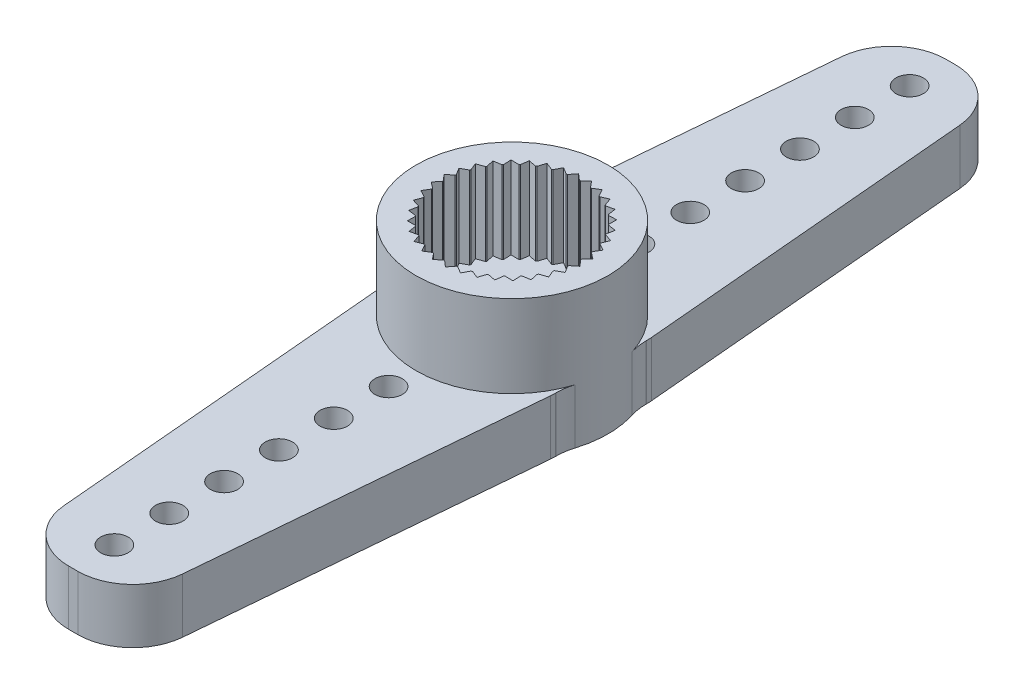
SolidWorks part; units mm, degrees
ref_plane "Front Plane" through (0, 0, 0) normal (0, 0, 1) x (1, 0, 0)
ref_plane "Top Plane" through (0, 0, 0) normal (0, 1, 0) x (1, 0, 0)
ref_plane "Right Plane" through (0, 0, 0) normal (1, 0, 0) x (0, 0, -1)
sketch "Sketch1" plane through (0, 0, 0) normal (0, 1, 0) x (1, 0, 0)
  line L0 (-21.777, 0) -> (33.3507, 0) construction
  line L1 (0, 26.1309) -> (0, -34.4991) construction
  line L2 (-17.4191, 16) -> (29.5794, 16) construction
  line L3 (-18.8664, -16) -> (33.3507, -16) construction
  line L4 (8.5, 26.926) -> (8.5, -27.618) construction
  line L5 (-8.5, 31.6087) -> (-8.5, -32.3009) construction
  line L6 (-24.067, 1.75) -> (35.98, 1.75) construction
  line L7 (-24.067, -1.75) -> (33.3507, -1.75) construction
  line L8 (-3.25, 29.5018) -> (-3.25, -36.5148) construction
  line L9 (3.25, 29.5018) -> (3.25, -33.8811) construction
  line L10 (-2, 29.5018) -> (-2, -51.2631) construction
  line L11 (2, 29.5018) -> (2, -51.2631) construction
  line L12 (-3.25, -1.75) -> (-3.25, 1.75)
  line L13 (-3.25, 1.75) -> (-2, 16)
  line L14 (-2, 16) -> (2, 16)
  line L15 (2, 16) -> (3.25, 1.75)
  line L16 (3.25, -1.75) -> (3.25, 1.75)
  line L19 (3.25, -1.75) -> (2, -16)
  line L20 (2, -16) -> (-2, -16)
  line L21 (-2, -16) -> (-3.25, -1.75)
  dimension "D1" = 16
  dimension "D2" = 16
  dimension "D3" = 8.5
  dimension "D4" = 8.5
  dimension "D5" = 1.75
  dimension "D6" = 1.75
  dimension "D7" = 3.25
  dimension "D8" = 3.25
  dimension "D9" = 2
  dimension "D10" = 2
extrude "Boss-Extrude1" add sketch "Sketch1" along normal blind 2
fillet "Fillet1" radius 2 4 edges at (-2, 1, -16) (2, 1, -16) (2, 1, 16) (-2, 1, 16)
sketch "Sketch2" plane through (0, 2, 0) normal (0, 1, 0) x (1, 0, 0)
  circle A0 centre (0, 0) radius 3.5
extrude "Boss-Extrude2" add sketch "Sketch2" along normal blind 3 and the other way blind 2
sketch "Sketch3" plane through (0, 0, 0) normal (0, -1, 0) x (-1, 0, 0)
  circle A0 centre (0, 0) radius 2.5
extrude "Cut-Extrude1" cut sketch "Sketch3" against normal blind 1
sketch "Sketch4" plane through (0, 1, 0) normal (0, -1, 0) x (-1, 0, 0)
  circle A0 centre (0, 0) radius 1
extrude "Cut-Extrude2" cut sketch "Sketch4" against normal through all
sketch "Sketch5" plane through (0, 5, 0) normal (0, 1, 0) x (1, 0, 0)
  circle A0 centre (0, 0) radius 2.5
extrude "Cut-Extrude3" cut sketch "Sketch5" against normal blind 3
sketch "Sketch6" plane through (0, 5, 0) normal (0, 1, 0) x (1, 0, 0)
  line L0 (-4.6624, 0) -> (4.5112, 0) construction
  line L1 (-5.0093, 0.3942) -> (0, 0) construction
  line L2 (0, 0) -> (6.4397, -0.5068) construction
  line L3 (0, 0) -> (-6.4046, 1.0144) construction
  line L4 (-2.5, 0) -> (-2.6917, 0.2118)
  line L5 (-2.6917, 0.2118) -> (-2.4692, 0.3911)
  line L6 (-2.4692, 0.3911) -> (-2.5, 0)
  circle A0 centre (0, 0) radius 2.7
  circle A1 centre (0, 0) radius 2.5 construction
  dimension "D1" = 4.5
  dimension "D2" = 4.5
extrude "Cut-Extrude4" cut sketch "Sketch6" against normal blind 3 contours L5 L6 L4
sketch "Sketch8" plane through (0, 0, 0) normal (1, 0, 0) x (0, 0, -1)
  line L0 (0, 0) -> (0, 8.8025) construction
pattern_circular "CirPattern1" count 36 over 360 about axis through (0, 0, 0) along (0, 1, 0) of "Cut-Extrude4"
sketch "Sketch9" plane through (0, 0, 0) normal (0, -1, 0) x (-1, 0, 0)
  circle A0 centre (0, 14.5) radius 0.5
  point P2 (0, 0)
  point P3 (0, 0)
extrude "Cut-Extrude5" cut sketch "Sketch9" against normal through all contours A0
sketch "Sketch10" plane through (0, 0, 0) normal (0, -1, 0) x (-1, 0, 0)
  line L0 (0, 13.2867) -> (0, -8.4466) construction
pattern_linear "LPattern1" count 6 spacing 2 along (0, 0, 1) of "Cut-Extrude5"
mirror "Mirror1" about plane through (0, 0, 0) normal (0, 0, 1) of "LPattern1"
fillet "Fillet3" radius 2 8 edges at (3.25, 1, -1.75) (3.25, 1, -1.299) (3.25, 1, 1.299) (3.25, 1, 1.75) (-3.25, 1, -1.75) (-3.25, 1, -1.299) (-3.25, 1, 1.299) (-3.25, 1, 1.75)
